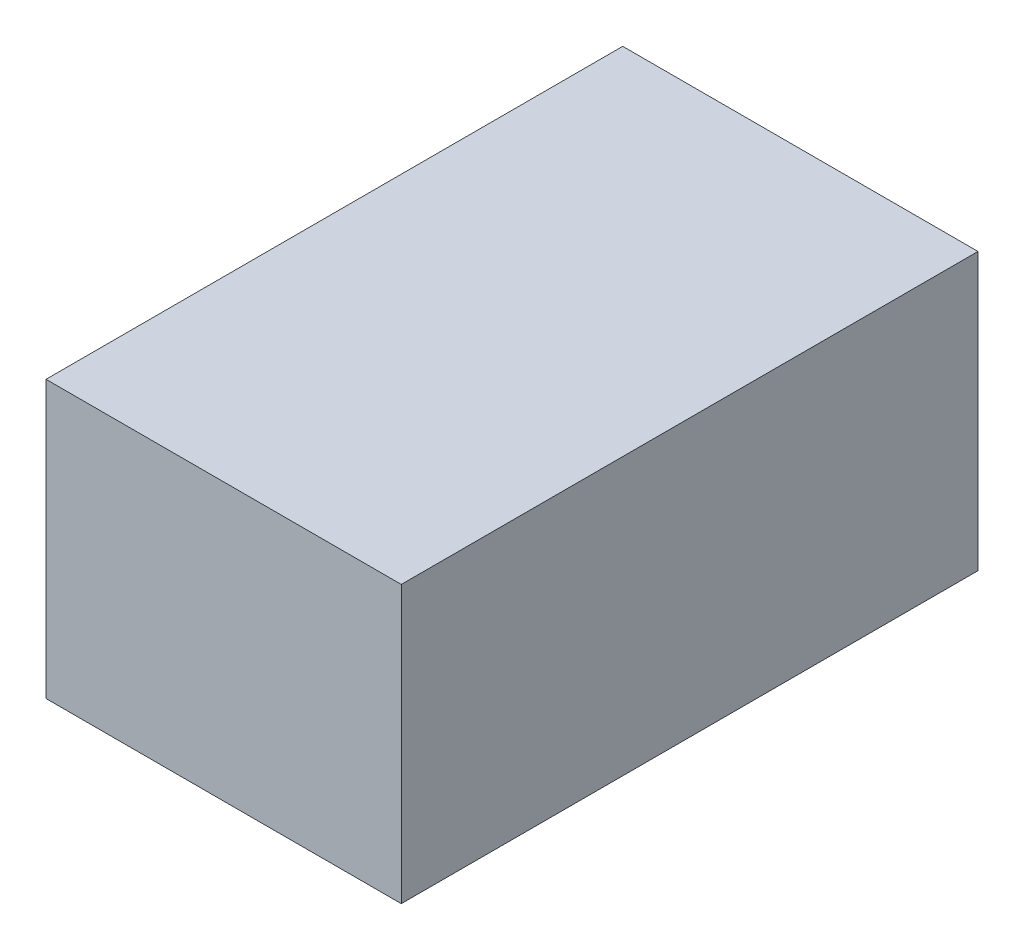
SolidWorks part; units mm, degrees
ref_plane "Front Plane" through (0, 0, 0) normal (0, 0, 1) x (1, 0, 0)
ref_plane "Top Plane" through (0, 0, 0) normal (0, 1, 0) x (1, 0, 0)
ref_plane "Right Plane" through (0, 0, 0) normal (1, 0, 0) x (0, 0, -1)
sketch "Sketch1" plane through (0, 0, 0) normal (0, 0, 1) x (1, 0, 0)
  line L1 (0, 0) -> (61.6032, 0)
  line L2 (0, 0) -> (0, 47.9423)
  line L3 (0, 47.9423) -> (61.6032, 47.9423)
  line L4 (61.6032, 0) -> (61.6032, 47.9423)
extrude "Boss-Extrude1" add sketch "Sketch1" along normal blind 100
